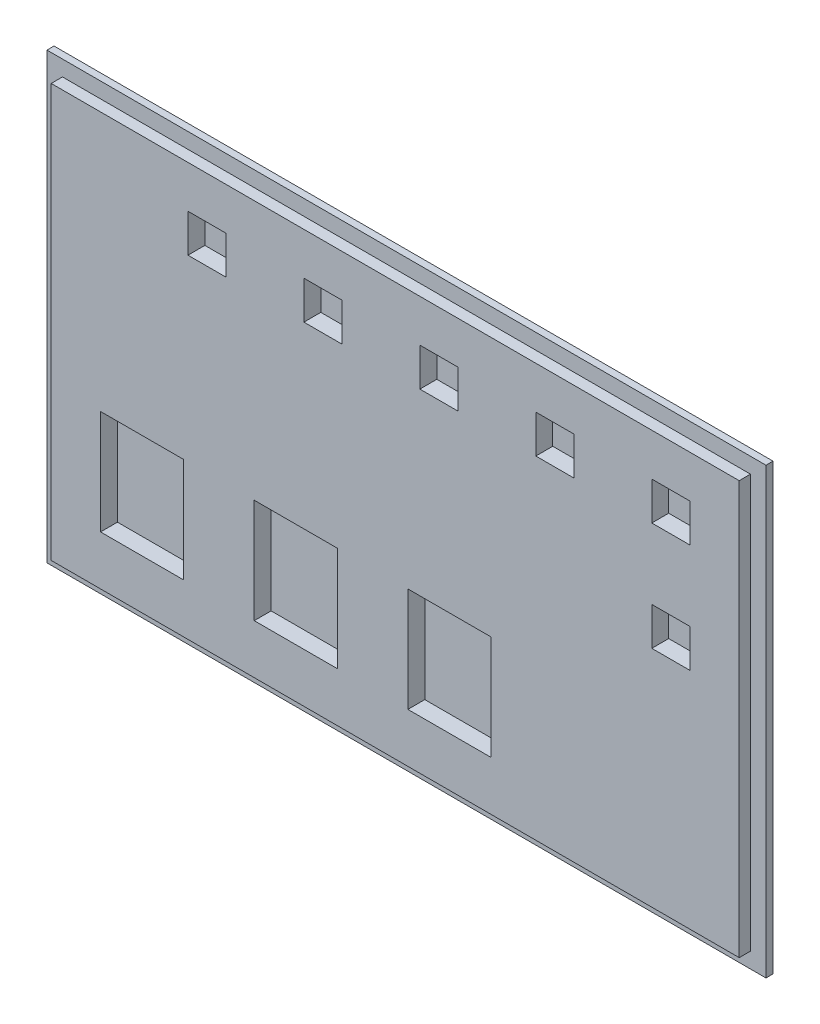
SolidWorks part; units mm, degrees
ref_plane "Přední rovina" through (0, 0, 0) normal (0, 0, 1) x (1, 0, 0)
ref_plane "Horní rovina" through (0, 0, 0) normal (0, 1, 0) x (1, 0, 0)
ref_plane "Pravá rovina" through (0, 0, 0) normal (1, 0, 0) x (0, 0, -1)
sketch "Skica1" plane through (0, 0, 0) normal (0, 0, 1) x (1, 0, 0)
  line L1 (0, 0) -> (102, 0)
  line L2 (0, 0) -> (0, 63)
  line L3 (0, 63) -> (102, 63)
  line L4 (102, 0) -> (102, 63)
  line L25 (21.6, 54.8) -> (27, 54.8)
  line L26 (21.6, 54.8) -> (21.6, 49.4)
  line L27 (21.6, 49.4) -> (27, 49.4)
  line L28 (27, 54.8) -> (27, 49.4)
  line L29 (38.05, 54.8) -> (43.45, 54.8)
  line L30 (38.05, 54.8) -> (38.05, 49.4)
  line L31 (38.05, 49.4) -> (43.45, 49.4)
  line L32 (43.45, 54.8) -> (43.45, 49.4)
  line L33 (54.5, 54.8) -> (59.9, 54.8)
  line L34 (54.5, 54.8) -> (54.5, 49.4)
  line L35 (54.5, 49.4) -> (59.9, 49.4)
  line L36 (59.9, 54.8) -> (59.9, 49.4)
  line L37 (70.95, 54.8) -> (76.35, 54.8)
  line L38 (70.95, 54.8) -> (70.95, 49.4)
  line L39 (70.95, 49.4) -> (76.35, 49.4)
  line L40 (76.35, 54.8) -> (76.35, 49.4)
  line L41 (87.4, 54.8) -> (92.8, 54.8)
  line L42 (87.4, 54.8) -> (87.4, 49.4)
  line L43 (87.4, 49.4) -> (92.8, 49.4)
  line L44 (92.8, 54.8) -> (92.8, 49.4)
  line L45 (2.2, 60.8) -> (99.8, 60.8)
  line L46 (2.2, 60.8) -> (2.2, 2.2)
  line L47 (2.2, 2.2) -> (99.8, 2.2)
  line L48 (99.8, 60.8) -> (99.8, 2.2)
  line L49 (9.2, 24) -> (21, 24)
  line L50 (9.2, 24) -> (9.2, 9.2)
  line L51 (9.2, 9.2) -> (21, 9.2)
  line L52 (21, 24) -> (21, 9.2)
  line L53 (31, 24) -> (42.8, 24)
  line L54 (31, 24) -> (31, 9.2)
  line L55 (31, 9.2) -> (42.8, 9.2)
  line L56 (42.8, 24) -> (42.8, 9.2)
  line L57 (52.8, 24) -> (64.6, 24)
  line L58 (52.8, 24) -> (52.8, 9.2)
  line L59 (52.8, 9.2) -> (64.6, 9.2)
  line L60 (64.6, 24) -> (64.6, 9.2)
  line L63 (87.4, 39.4) -> (92.8, 39.4)
  line L65 (87.4, 39.4) -> (87.4, 34)
  line L66 (87.4, 34) -> (92.8, 34)
  line L67 (92.8, 39.4) -> (92.8, 34)
  point P29 (90.1, 54.8)
  dimension "D2" = 5.4
  dimension "D3" = 5.4
  dimension "D4" = 7
  dimension "D5" = 6
  dimension "D6" = 5.4
  dimension "D7" = 5.4
  dimension "D8" = 5.4
  dimension "D9" = 5.4
  dimension "D10" = 5.4
  dimension "D11" = 5.4
  dimension "D12" = 5.4
  dimension "D13" = 5.4
  dimension "D14" = 11.05
  dimension "D15" = 102
  dimension "D16" = 11.05
  dimension "D17" = 11.05
  dimension "D18" = 63
  dimension "D19" = 11.05
  dimension "D20" = 2.2
  dimension "D21" = 2.2
  dimension "D22" = 2.2
  dimension "D23" = 2.2
  dimension "D24" = 6
  dimension "D25" = 11.8
  dimension "D26" = 14.8
  dimension "D27" = 11.8
  dimension "D28" = 11.8
  dimension "D32" = 7
  dimension "D33" = 7
  dimension "D34" = 10
  dimension "D35" = 10
  dimension "D36" = 5.4
  dimension "D37" = 5.4
  dimension "D38" = 10
  dimension "D39" = 97.6
extrude "Přidat vysunutím1" add sketch "Skica1" along normal blind 2.6 contours L48 L45 L46 L47 L25 L28 L27 L26 L29 L32 L31 L30 L33 L36 L35 L34 L37 L40 L39 L38 L41 L44 L43 L42 L49 L52 L51 L50 L53 L56 L55 L54 L57 L60 L59 L58 region at (52.0643, 32.4265, 0)
extrude "Přidat vysunutím2" add sketch "Skica1<3>" along normal blind 1 contours L1 L4 L3 L2 L45 L48 L47 L46 region at (1.1989, 31.5, 0)
sketch "Skica1<3>" plane through (0, 0, 0) normal (0, 0, 1) x (1, 0, 0) same geometry as "Skica1"
extrude "Přidat vysunutím3" add sketch "Skica1<5>" along normal blind 0.2 contours L58 L59 L60 | L54 L55 L56 | L52 L50 L51 | L67 L63 L65 L66 | L44 L41 L42 L43 | L40 L37 L38 L39 | L36 L33 L34 L35 | L32 L29 L30 L31 | L28 L25 L26 L27 region at (24.3, 52.1, 0) region at (40.75, 52.1, 0) region at (57.2, 52.1, 0) region at (73.65, 52.1, 0) region at (90.1, 52.1, 0) region at (15.1, 16.6, 0) region at (36.9, 16.6, 0) region at (58.7, 16.6, 0) region at (90.1, 36.7, 0)
sketch "Skica1<5>" plane through (0, 0, 0) normal (0, 0, 1) x (1, 0, 0) same geometry as "Skica1"
